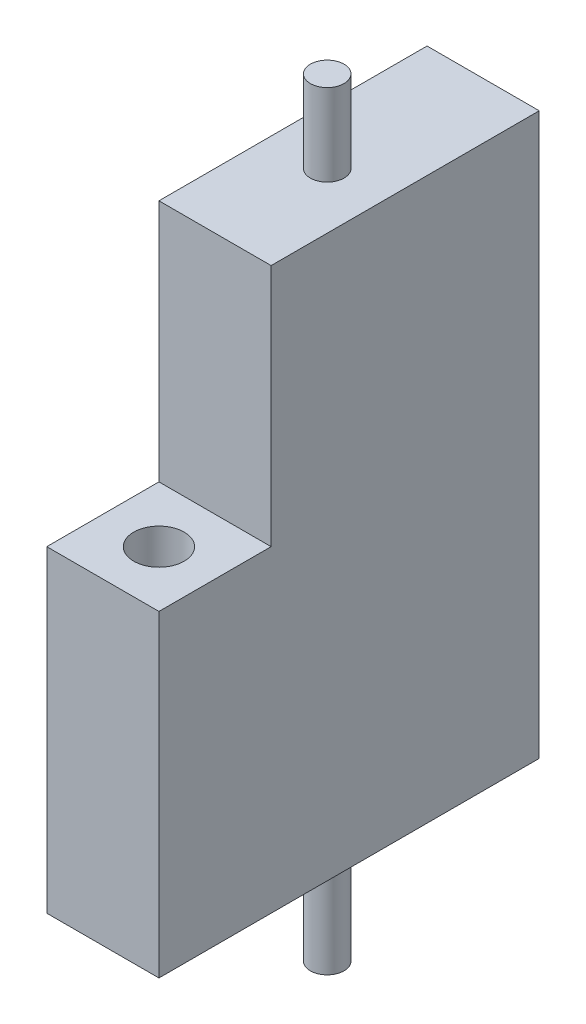
SolidWorks part; units mm, degrees
ref_plane "前视基准面" through (0, 0, 0) normal (0, 0, 1) x (1, 0, 0)
ref_plane "上视基准面" through (0, 0, 0) normal (0, 1, 0) x (1, 0, 0)
ref_plane "右视基准面" through (0, 0, 0) normal (1, 0, 0) x (0, 0, -1)
sketch "草图1" plane through (0, 0, 0) normal (0, 0, 1) x (1, 0, 0)
  line L0 (22.5, 0) -> (22.5, 287.3668) construction
  line L1 (0, 0) -> (16.5, 0)
  line L2 (0, 0) -> (0, 10)
  line L3 (0, 10) -> (16.5, 10)
  line L4 (16.5, 0) -> (16.5, 10)
  line L5 (16.5, 0) -> (28.5, 0)
  line L6 (16.5, 0) -> (16.5, 10)
  line L7 (16.5, 10) -> (28.5, 10)
  line L8 (28.5, 0) -> (28.5, 10)
  line L9 (28.5, 10) -> (45, 10)
  line L10 (28.5, 10) -> (28.5, 0)
  line L11 (28.5, 0) -> (45, 0)
  line L12 (45, 10) -> (45, 0)
  line L13 (0, 10) -> (1, 10)
  line L14 (0, 10) -> (0, 102)
  line L15 (0, 102) -> (1, 102)
  line L16 (1, 10) -> (1, 102)
  line L17 (1, 102) -> (44, 102)
  line L18 (1, 102) -> (1, 10)
  line L19 (1, 10) -> (44, 10)
  line L20 (44, 102) -> (44, 10)
  line L21 (44, 102) -> (45, 102)
  line L22 (44, 102) -> (44, 10)
  line L23 (44, 10) -> (45, 10)
  line L24 (45, 102) -> (45, 10)
  line L25 (0, 0) -> (-10, 0)
  line L26 (0, 0) -> (0, 250)
  line L27 (0, 250) -> (-10, 250)
  line L28 (-10, 0) -> (-10, 250)
  line L29 (45, 0) -> (55, 0)
  line L30 (45, 0) -> (45, 250)
  line L31 (45, 250) -> (55, 250)
  line L32 (55, 0) -> (55, 250)
  line L33 (-10, 250) -> (55, 250)
  line L34 (-10, 250) -> (-10, 260)
  line L35 (-10, 260) -> (55, 260)
  line L36 (55, 260) -> (55, 250)
  line L37 (-10, 250) -> (55, 250)
  line L46 (-27.5, 0) -> (72.5, 0)
  line L47 (147.5, 475.7809) -> (197.5, 475.7809)
  line L52 (147.5, 475.7809) -> (172.5, 475.7809)
  line L56 (72.5, 0) -> (-27.5, 0)
  line L57 (72.5, 0) -> (72.5, 250)
  line L58 (72.5, 250) -> (-27.5, 250)
  line L59 (-27.5, 0) -> (-27.5, 250)
  line L60 (-27.5, 0) -> (72.5, 0)
  line L61 (-27.5, 0) -> (-27.5, -33)
  line L62 (-27.5, -33) -> (72.5, -33)
  line L63 (72.5, 250) -> (72.5, 0)
  line L64 (72.5, 0) -> (72.5, -33)
  point P21 (22.5, 0)
  dimension "D1" = 16.5
  dimension "D2" = 12
  dimension "D3" = 16.5
  dimension "D4" = 10
  dimension "D5" = 1
  dimension "D6" = 43
  dimension "D7" = 92
  dimension "D8" = 10
  dimension "D9" = 250
  dimension "D10" = 10
  dimension "D11" = 250
  dimension "D12" = 10
  dimension "D13" = 50
  dimension "D16" = 33
revolve "旋转1" add sketch "草图1" angle 360 about L0 region at (8.25, 5, 0) region at (-5, 125, 0) region at (0.5, 56, 0) region at (36.75, 5, 0) region at (50, 125, 0) region at (44.5, 56, 0)
sketch "草图2" plane through (0, 0, 0) normal (0, -1, 0) x (1, 0, 0)
  line L0 (28.5, 0) -> (30.2, 0)
  line L1 (28.5, 2) -> (28.1569, 2)
  line L2 (28.5, 0) -> (30.2, 0)
  line L3 (28.5, 0) -> (28.5, 2)
  line L4 (28.5, 2) -> (30.2, 2)
  line L5 (30.2, 0) -> (30.2, 2)
  line L6 (28.5, 0) -> (30.2, 0)
  line L7 (28.5, 0) -> (28.5, -2)
  line L8 (28.5, -2) -> (30.2, -2)
  line L9 (30.2, 0) -> (30.2, -2)
  line L10 (28.1569, 2) -> (28.1569, -2)
  line L11 (28.1569, -2) -> (28.5, -2)
  circle A0 centre (22.5, 0) radius 6 construction
  circle M11 centre (22.5, 0) radius 6
  dimension "D1" = 1.7
  dimension "D2" = 2
  dimension "D3" = 2
extrude "切除-拉伸1" cut sketch "草图2" against normal blind 10 contours L9 L0 L7 L8 | L11 L7 M11 | L3 L1 M11 | L0 L5 L4 L3 region at (29.35, 0, 1) region at (28.3976, 0, 1.5029) region at (29.35, 0, -1) region at (28.3976, 0, -1.5029)
sketch "草图3" plane through (0, 250, 0) normal (0, 1, 0) x (1, 0, 0)
  line L0 (-27.5, 0) -> (72.5, 0) construction
  line L1 (-27.5, 0) -> (22.5, 0)
  line L4 (22.5, 0) -> (22.5, 32.5)
  line L5 (72.5, 0) -> (-27.5, 0) construction
  line L6 (72.5, 0) -> (-27.5, 0) construction
  line L8 (22.5, 32.5) -> (22.5, 0)
  line L9 (22.5, 0) -> (72.5, 0)
  line L12 (22.5, 0) -> (72.5, 0)
  line L13 (22.5, 0) -> (22.5, -32.5)
  line L17 (22.5, -32.5) -> (22.5, 0)
  line L18 (22.5, 0) -> (-27.5, 0)
  line L20 (22.5, 0) -> (-27.5, 0)
  line L21 (22.5, 0) -> (22.5, 50)
  line L22 (22.5, 50) -> (-27.5, 50)
  line L23 (-27.5, 0) -> (-27.5, 50)
  line L24 (22.5, 0) -> (72.5, 0)
  line L25 (22.5, 0) -> (22.5, -50)
  line L26 (22.5, -50) -> (72.5, -50)
  line L27 (72.5, 0) -> (72.5, -50)
  line L28 (-27.5, 50) -> (72.5, 50)
  line L29 (-27.5, 50) -> (-27.5, -50)
  line L30 (-27.5, -50) -> (72.5, -50)
  line L31 (72.5, 50) -> (72.5, -50)
  circle A0 centre (22.5, 0) radius 32.5 construction
  circle A1 centre (22.5, 0) radius 32.5
  circle A2 centre (22.5, 0) radius 50
  circle M1 centre (22.5, 0) radius 32.5
  dimension "D1" = 100
  dimension "D5" = 50
extrude "凸台-拉伸1" add sketch "草图3" against normal blind 250 contours L23 L1 M1 | L1 M1 | L27 L9 M1 | L9 M1 region at (-4.1544, 250, -26.6544) region at (-4.1544, 250, 26.6544) region at (49.1544, 250, -26.6544) region at (49.1544, 250, 26.6544)
extrude "凸台-拉伸7" add sketch "草图3<5>" against normal blind 250 contours A2 L26 L27 | A2 L29 L30 | A2 L31 L28 | A2 L22 L23 region at (-16.3316, 250, 38.8316) region at (-16.3316, 250, -38.8316) region at (61.3316, 250, -38.8316) region at (61.3316, 250, 38.8316)
sketch "草图3<5>" plane through (0, 250, 0) normal (0, 1, 0) x (1, 0, 0) same geometry as "草图3"
extrude "凸台-拉伸8" add sketch "草图1<21>" along normal blind 50 and the other way blind 50 contours L64 L46 L29 L11 L5 L1 L25 L61 L62 region at (22.5, -16.5, 0)
sketch "草图1<21>" plane through (0, 0, 0) normal (0, 0, 1) x (1, 0, 0) same geometry as "草图1"
sketch "草图5" plane through (0, -33, 0) normal (0, -1, 0) x (1, 0, 0)
  line L0 (-10, 0) -> (55, 0) construction
  line L1 (-27.5, 0) -> (72.5, 0)
  line L2 (22.5, -50) -> (22.5, 50)
  line L3 (-27.5, 0) -> (22.5, -50) construction
  line L4 (-27.5, 0) -> (22.5, 50) construction
  line L5 (22.5, -50) -> (72.5, 0) construction
  line L6 (22.5, 50) -> (72.5, 0) construction
  line L7 (-2.5, 25) -> (-6.9901, 29.4901)
  line L8 (-12.8553, 35.3553) -> (57.8553, -35.3553)
  line L9 (22.5, 50) -> (22.5, -50)
  line L10 (57.8553, 35.3553) -> (-12.8553, -35.3553)
  line L11 (72.5, 0) -> (-27.5, 0)
  line L12 (57.8553, -35.3553) -> (-12.8553, 35.3553)
  line L13 (22.5, -50) -> (22.5, 50)
  line L14 (-12.8553, -35.3553) -> (57.8553, 35.3553)
  circle A0 centre (22.5, 0) radius 50 construction
  circle A1 centre (-4.7451, 27.2451) radius 3.175 construction
  circle A2 centre (-4.7451, 27.2451) radius 4.77
  circle A3 centre (22.5, 38.5303) radius 4.77
  circle A4 centre (49.7451, 27.2451) radius 4.77
  circle A5 centre (61.0303, 0) radius 4.77
  circle A6 centre (49.7451, -27.2451) radius 4.77
  circle A7 centre (22.5, -38.5303) radius 4.77
  circle A8 centre (-4.7451, -27.2451) radius 4.77
  circle A9 centre (-16.0303, 0) radius 4.77
  point P43 (22.5, 0)
  dimension "D2" = 8
extrude "切除-拉伸2" cut sketch "草图5" against normal blind 9.525 contours L14 A8 | L14 A8 | L13 A7 | L13 A7 | L12 A6 | L12 A6 | L11 A5 | L11 A5 | L14 A4 | L14 A4 | L13 A3 | L13 A3 | L12 A2 L8 L7 | L8 A2 L12 L7 | L11 A9 | L11 A9 region at (-16.0303, -33, 2.0245) region at (-6.1766, -33, 25.8136) region at (-3.3136, -33, 28.6766) region at (20.4755, -33, 38.5303) region at (24.5245, -33, 38.5303) region at (48.3136, -33, 28.6766) region at (51.1766, -33, 25.8136) region at (61.0303, -33, 2.0245) region at (61.0303, -33, -2.0245) region at (51.1766, -33, -25.8136) region at (48.3136, -33, -28.6766) region at (24.5245, -33, -38.5303) region at (20.4755, -33, -38.5303) region at (-3.3136, -33, -28.6766) region at (-6.1766, -33, -25.8136) region at (-16.0303, -33, -2.0245)
sketch "草图7" plane through (0, -33, 0) normal (0, -1, 0) x (1, 0, 0)
  line L1 (49.7451, -27.2451) -> (44.9751, -27.2451) construction
  line L2 (49.7451, -27.2451) -> (49.7451, -22.4751) construction
  line L3 (49.7451, -22.4751) -> (44.9751, -22.4751) construction
  line L4 (44.9751, -27.2451) -> (44.9751, -22.4751) construction
  line L5 (-4.7451, 27.2451) -> (0.0249, 27.2451) construction
  line L6 (-4.7451, 27.2451) -> (-4.7451, 22.4751) construction
  line L7 (-4.7451, 22.4751) -> (0.0249, 22.4751) construction
  line L8 (0.0249, 27.2451) -> (0.0249, 22.4751) construction
  line L9 (0.0249, 22.4751) -> (44.9751, 22.4751)
  line L10 (0.0249, 22.4751) -> (0.0249, -22.4751)
  line L11 (0.0249, -22.4751) -> (44.9751, -22.4751)
  line L12 (44.9751, 22.4751) -> (44.9751, -22.4751)
  circle A0 centre (49.7451, -27.2451) radius 4.77 construction
  circle A1 centre (49.7451, -27.2451) radius 4.77 construction
  circle A2 centre (-4.7451, 27.2451) radius 4.77 construction
  circle A3 centre (-4.7451, 27.2451) radius 4.77 construction
  point P0 (44.9751, -27.2451)
  point P1 (49.7451, -22.4751)
  point P10 (-4.7451, 22.4751)
  point P11 (0.0249, 27.2451)
extrude "切除-拉伸3" cut sketch "草图7" against normal blind 33
sketch "草图8" plane through (72.5, 0, 0) normal (1, 0, 0) x (0, 0, -1)
  line L0 (0, -33) -> (150, -33)
  line L1 (50, -33) -> (-50, -33) construction
  line L3 (150, -33) -> (135, -33)
  line L4 (150, -33) -> (150, 467)
  line L5 (150, 467) -> (135, 467)
  line L6 (135, -33) -> (135, 467)
  dimension "D1" = 150
  dimension "D2" = 15
  dimension "D3" = 500
sketch "草图9" plane through (0, 250, 0) normal (0, 1, 0) x (1, 0, 0)
sketch "草图10" plane through (0, 250, 0) normal (0, 1, 0) x (1, 0, 0)
  line L0 (72.5, 150) -> (72.5, 135) construction
  line L1 (22.5, 0) -> (72.5, 0) construction
  line L2 (22.5, 0) -> (22.5, 135) construction
  line L3 (22.5, 135) -> (72.5, 135) construction
  line L4 (72.5, 0) -> (72.5, 135) construction
sketch "草图12" plane through (0, 0, -50) normal (0, 0, -1) x (-1, 0, 0)
  line L0 (-72.5, -33) -> (-72.5, 467) construction
  line L1 (-72.5, 467) -> (27.5, 467)
  line L2 (-72.5, 467) -> (-72.5, -33)
  line L3 (-72.5, -33) -> (27.5, -33)
  line L4 (27.5, 467) -> (27.5, -33)
  line L5 (-72.5, -33) -> (-72.5, 467) construction
  line L6 (27.5, -33) -> (-72.5, -33) construction
  line L7 (27.5, -33) -> (27.5, 250) construction
extrude "凸台-拉伸10" add sketch "草图12" along normal blind 239
sketch "草图13" plane through (0, 467, 0) normal (0, 1, 0) x (1, 0, 0)
  line L0 (72.5, 150) -> (72.5, 135) construction
  line L1 (72.5, 150) -> (22.5, 150)
  line L2 (72.5, 150) -> (72.5, 135)
  line L3 (72.5, 135) -> (22.5, 135)
  line L4 (22.5, 150) -> (22.5, 135)
  circle A2 centre (22.5, 150) radius 15
extrude "凸台-拉伸12" add sketch "草图13" against normal blind 612 and the other way blind 73 contours L4 A2 L3 | L3 A2 L4 region at (28.8662, 467, -143.6338) region at (20.3779, 467, -152.1221)
